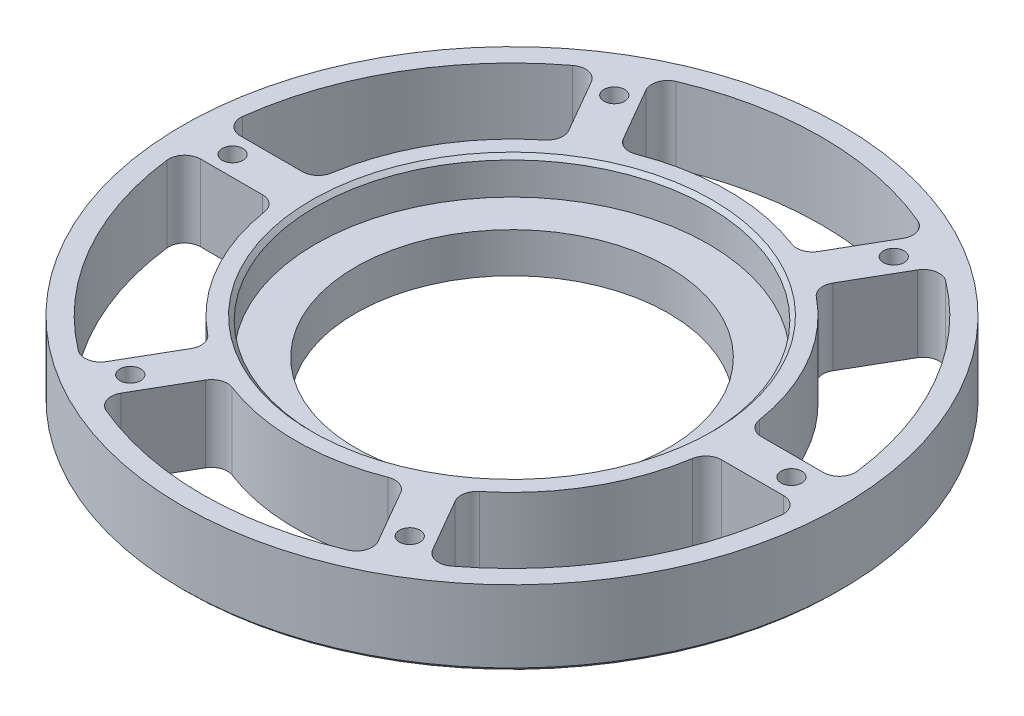
SolidWorks part; units mm, degrees
material "6061-T6 (SS)"
ref_plane "Front Plane" through (0, 0, 0) normal (0, 0, 1) x (1, 0, 0)
ref_plane "Top Plane" through (0, 0, 0) normal (0, 1, 0) x (1, 0, 0)
ref_plane "Right Plane" through (0, 0, 0) normal (1, 0, 0) x (0, 0, -1)
sketch "Sketch2" plane through (0, 0, 0) normal (1, 0, 0) x (0, 0, -1)
  line L0 (-39.2125, 0) -> (-82.55, 0)
  line L1 (-82.55, 0) -> (-82.55, 19.05)
  line L2 (-82.55, 19.05) -> (-49.2125, 19.05)
  line L3 (-49.2125, 19.05) -> (-49.2125, 10)
  line L4 (-49.2125, 10) -> (-39.2125, 10)
  line L5 (-39.2125, 10) -> (-39.2125, 0)
  dimension "D1" = 82.55
  dimension "D2" = 19.05
  dimension "D4" = 49.2125
  dimension "D5" = 10
  dimension "D3" = 10
ref_axis "Axis1" through (0, -0.9525, 0) along (0, 1, 0)
revolve "Revolve1" add sketch "Sketch2" angle 360 about axis through (0, -0.9525, 0) along (0, 1, 0)
hole_wizard "#6 (0.204) Diameter Hole1" positions "Sketch6" profile "Sketch7" hole size "#6" standard "ANSI Inch" end condition through all
sketch "Sketch6" plane through (0, 19.05, 0) normal (0, 1, 0) x (1, 0, 0)
  line L0 (0, 0) -> (-69.8201, 120.932) construction
  line L2 (0, 0) -> (0, 109.0908) construction
  point P0 (-35, 60.6218)
  dimension "D1" = 30
  dimension "D2" = 70
sketch "Sketch7" plane through (-35, 19.05, -60.6218) normal (1, 0, 0) x (0, 0, 1)
  line L0 (0, 0) -> (0, 19.05)
  line L1 (0, 19.05) -> (2.5908, 19.05)
  line L2 (2.5908, 19.05) -> (2.5908, 0)
  line L5 (2.5908, 0) -> (0, 0)
  line L11 (0, -6.35) -> (0, 107.95) construction
  dimension "Thru Hole Dia." = 5.1816
  dimension "Thru Hole Depth" = 19.05
pattern_circular "CirPattern3" count 6 over 360 about axis through (0, -0.9525, 0) along (0, 1, 0) of "#6 (0.204) Diameter Hole1"
sketch "Sketch8" plane through (0, 19.05, 0) normal (0, 1, 0) x (1, 0, 0)
  line L0 (-34.3642, 69.5205) -> (-22.6606, 49.2493)
  line L1 (34.3642, 69.5205) -> (22.6606, 49.2493)
  line L2 (0, 0) -> (-35, 60.6218) construction
  line L4 (0, 0) -> (0, 93.9995) construction
  arc A0 (-22.6606, 49.2493) -> (22.6606, 49.2493) centre (0, 0) cw
  arc A1 (-34.3642, 69.5205) -> (34.3642, 69.5205) centre (0, 0) cw
  circle A2 centre (0, 0) radius 49.2125 construction
  circle A3 centre (0, 0) radius 82.55 construction
  dimension "D1" = 5
  dimension "D2" = 5
  dimension "D3" = 5
extrude "Cut-Extrude1" cut sketch "Sketch8" against normal through all
fillet "Fillet1" radius 4 4 edges at (34.3642, 9.525, -69.5205) (22.6606, 9.525, -49.2493) (-34.3642, 9.525, -69.5205) (-22.6606, 9.525, -49.2493)
pattern_circular "CirPattern4" count 6 over 360 about axis through (0, -0.9525, 0) along (0, 1, 0) of "Cut-Extrude1", "Fillet1"
chamfer "Chamfer1" distance 1 angle 45 1 edges at (0, 19.05, -49.2125)
chamfer "Chamfer2" distance 1 angle 45 1 edges at (0, 0, -82.55)
equation "\"TubeDiameter\" = 6.500in"
equation "\"D1@Sketch2\"=\"TubeDiameter\"/2"
